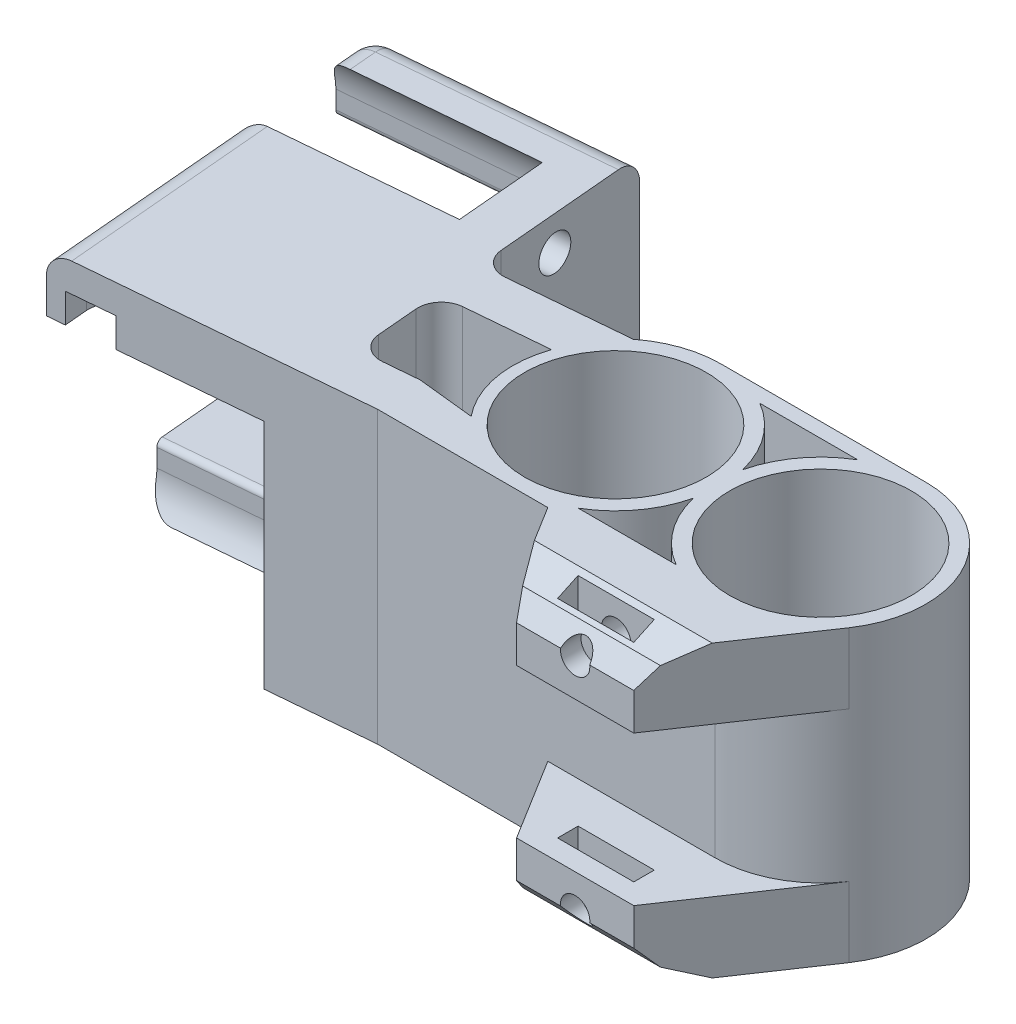
SolidWorks part; units mm, degrees
ref_plane "Front" through (0, 0, 0) normal (0, 0, 1) x (1, 0, 0)
ref_plane "Top" through (0, 0, 0) normal (0, 1, 0) x (1, 0, 0)
ref_plane "Right" through (0, 0, 0) normal (1, 0, 0) x (0, 0, -1)
sketch "Sketch1" plane through (0, 0, 0) normal (0, 1, 0) x (1, 0, 0)
  line L0 (0, 0) -> (17.5, 0) construction
  line L1 (0, 9) -> (17.5, 9)
  line L4 (0, -9) -> (17.5, -9)
  line L5 (0, -7.75) -> (17.5, -7.75)
  line L6 (0, 7.75) -> (17.5, 7.75)
  circle A6 centre (0, 0) radius 7.75
  circle A8 centre (0, 0) radius 7.75
  circle A10 centre (0, 0) radius 9
  circle A12 centre (17.5, 0) radius 7.75
  arc A13 (0, 9) -> (0, -9) centre (0, 0) ccw
  arc A14 (17.5, -9) -> (17.5, 9) centre (17.5, 0) ccw
  circle A15 centre (0, 0) radius 7.5 construction
  circle A16 centre (17.5, 0) radius 9
  point P5 (8.75, 0)
  dimension "D1" = 15.5
  dimension "D2" = 15.5
  dimension "D3" = 1.5
extrude "Boss-Extrude1" add sketch "Sketch1" along normal blind 24
sketch "Sketch2" plane through (0, 0, 0) normal (0, -1, 0) x (1, 0, 0)
  line L2 (17.5, 9) -> (0, 9)
  line L3 (0, -9) -> (17.5, -9)
  line L4 (17.5, 9) -> (0, 9)
  line L5 (0, -9) -> (17.5, -9)
  circle A0 centre (17.5, 0) radius 4.33 construction
  circle A1 centre (0, 0) radius 4.33 construction
  circle A2 centre (17.5, 0) radius 4.33
  circle A3 centre (0, 0) radius 4.33
  arc A6 (0, 9) -> (0, -9) centre (0, 0) ccw
  arc A7 (17.5, -9) -> (17.5, 9) centre (17.5, 0) ccw
  arc A8 (0, 9) -> (0, -9) centre (0, 0) ccw
  arc A9 (17.5, -9) -> (17.5, 9) centre (17.5, 0) ccw
  dimension "D1" = 0
extrude "Boss-Extrude2" add sketch "Sketch2" along normal blind 0.75
sketch "Sketch4" plane through (0, 0, 9) normal (0, 0, 1) x (1, 0, 0)
  line L0 (12.5625, -0.75) -> (12.5625, 24) construction
  line L1 (17.5, -0.75) -> (0, -0.75) construction
  line L3 (12.5625, 24) -> (12.5625, 11.625) construction
  line L4 (12.5625, 11.625) -> (0, 11.625) construction
  line L5 (0, 24) -> (0, -0.75) construction
  line L6 (17.5625, 5.25) -> (17.5625, -0.75)
  line L7 (17.5625, 5.25) -> (7.5625, 5.25)
  line L8 (17.5625, -0.75) -> (7.5625, -0.75)
  line L9 (7.5625, 5.25) -> (7.5625, -0.75)
  line L10 (17.5625, 5.25) -> (7.5625, -0.75) construction
  line L11 (17.5625, -0.75) -> (7.5625, 5.25) construction
  line L12 (17.5625, 18) -> (17.5625, 24)
  line L13 (17.5625, 24) -> (7.5625, 24)
  line L14 (7.5625, 18) -> (7.5625, 24)
  line L15 (17.5625, 18) -> (7.5625, 18)
  line L16 (16.1875, -135.4345) -> (16.1875, -151.4345) construction
  line L17 (8.9375, -151.4345) -> (8.9375, -135.4345) construction
  line L18 (16.1875, -135.4345) -> (16.1875, -151.4345) construction
  line L19 (8.9375, -151.4345) -> (8.9375, -135.4345) construction
  line L20 (8.9375, -143.4345) -> (16.1875, -143.4345) construction
  line L21 (16.1875, -143.4345) -> (12.5625, -143.4345) construction
  line L22 (12.5625, -143.4345) -> (12.5625, -5.1253) construction
  point P11 (12.5625, 2.25)
  dimension "D1" = 6
  dimension "D2" = 10
extrude "Boss-Extrude4" add sketch "Sketch4" along normal blind 7
sketch "Sketch5" plane through (0, 18, 0) normal (0, -1, 0) x (1, 0, 0)
  line L0 (9.3125, 12.5) -> (15.8125, 12.5)
  line L1 (9.3125, 12.5) -> (9.3125, 14.25)
  line L2 (15.8125, 12.5) -> (15.8125, 14.25)
  line L3 (9.3125, 14.25) -> (15.8125, 14.25)
  line L5 (12.5625, 16) -> (12.5625, 12.5) construction
  line L6 (7.5625, 16) -> (17.5625, 16) construction
  line L8 (7.5625, 9) -> (17.5, 9) construction
  dimension "D1" = 6.5
  dimension "D2" = 1.75
  dimension "D3" = 3.5
extrude "Cut-Extrude1" cut sketch "Sketch5" against normal through all both and the other way through all
sketch "Sketch6" plane through (0, 0, 16) normal (0, 0, 1) x (1, 0, 0)
  line L1 (7.5625, -0.75) -> (17.5625, -0.75) construction
  line L2 (17.5625, 24) -> (7.5625, 24) construction
  line L3 (12.5625, 24) -> (12.5625, 11.625) construction
  line L4 (12.5625, 11.625) -> (16.3282, 11.625) construction
  line L5 (12.5625, -0.75) -> (12.5625, 5.25) construction
  line L6 (17.5625, 5.25) -> (7.5625, 5.25) construction
  circle A0 centre (12.5625, 2.25) radius 1.25
  circle A1 centre (12.5625, 21) radius 1.25
  dimension "D1" = 2.5
extrude "Cut-Extrude2" cut sketch "Sketch6" against normal offset from surface (19 mm away) 6 up to face at (8.75, 11.625, -9)
sketch "Sketch7" plane through (0, 24, 0) normal (0, 1, 0) x (1, 0, 0)
  line L0 (-8.2702, -8.7348) -> (-9.6225, 6.7225) construction
  line L1 (8.75, 9) -> (8.75, 26.8601) construction
  line L2 (0, 9) -> (17.5, 9) construction
  line L3 (-8.2702, -8.7348) -> (-9.6225, 6.7225)
  line L4 (-8.2702, -8.7348) -> (-11.301, -9)
  line L5 (-9.6225, 6.7225) -> (16.4097, 9)
  line L6 (-6.5487, -14.069) -> (-8.9814, 13.7363)
  line L7 (-8.2702, -8.7348) -> (-9.6225, 6.7225)
  line L8 (-8.2702, -8.7348) -> (-20.2245, -9.7807)
  line L9 (-9.6225, 6.7225) -> (-21.5769, 5.6766)
  line L10 (-20.2245, -9.7807) -> (-21.5769, 5.6766)
  line L11 (0, 9) -> (17.5, 9) construction
  line L12 (0, 9) -> (17.5, 9)
  line L13 (7.5625, -9) -> (0, -9) construction
  line L14 (7.5625, -9) -> (0, -9)
  line L15 (0, -9) -> (-11.301, -9)
  line L22 (17.5625, -9) -> (17.5, -9)
  line L23 (17.5625, -9) -> (17.5, -9)
  line L24 (0, -9) -> (7.5625, -9)
  line L25 (7.5625, -9) -> (7.5625, -16)
  line L26 (0, -9) -> (7.5625, -9)
  line L27 (17.5, 9) -> (0, 9)
  line L28 (17.5625, -16) -> (17.5625, -9)
  line L29 (17.5625, -16) -> (17.5625, -9)
  line L30 (7.5625, -16) -> (17.5625, -16)
  line L31 (7.5625, -9) -> (7.5625, -16)
  line L32 (7.5625, -16) -> (17.5625, -16)
  line L33 (17.5, 9) -> (0, 9)
  arc A0 (0, 9) -> (0, -9) centre (0, 0) ccw construction
  circle A1 centre (0, 0) radius 7.75 construction
  arc A4 (17.5, -9) -> (17.5, 9) centre (17.5, 0) ccw
  arc A5 (0, 9) -> (0, -9) centre (0, 0) ccw
  arc A6 (17.5, -9) -> (17.5, 9) centre (17.5, 0) ccw
  arc A7 (0, 9) -> (0, -9) centre (0, 0) ccw
  line M21 (17.5, 9) -> (0, 9)
  arc M22 (0, 9) -> (0, -9) centre (0, 0) ccw
  dimension "D1" = 5
  dimension "D2" = 12
  dimension "D3" = 0
extrude "Boss-Extrude5" add sketch "Sketch7" against normal up to surface (24.75 mm away) contours L10 L8 L3 L9 | L6 L5 L3 M22 | L4 L6 L3 M22 | L6 M22 | L6 L5 M22 M21 | L15 L6 L4 M22
sketch "Sketch8" plane through (0, 24, 0) normal (0, 1, 0) x (1, 0, 0)
  line L1 (-11.6496, -5.0152) -> (-6.7762, -5.5359)
  line L2 (-11.301, -9) -> (-20.2245, -9.7807) construction
  line L3 (-11.301, -9) -> (-20.2245, -9.7807)
  line L4 (-20.2245, -9.7807) -> (-21.5769, 5.6766) construction
  line L5 (-20.2245, -9.7807) -> (-21.5769, 5.6766)
  line L8 (-11.6496, -5.0152) -> (-16.5884, -5.4473)
  line L9 (-16.5884, -5.4473) -> (-17.5921, 6.0252)
  line L11 (4.5758, 7.75) -> (12.9242, 7.75) construction
  line L12 (-5.2103, 3.0932) -> (-21.2282, 1.6918)
  line L13 (-8.2816, 2.8245) -> (-21.2282, 1.6918)
  line L14 (4.062, 7.75) -> (12.9242, 7.75)
  circle A2 centre (0, 0) radius 8.75
  circle A3 centre (0, 0) radius 8.75
  line M22 (4.5758, 7.75) -> (12.9242, 7.75)
  dimension "D1" = 4
  dimension "D2" = 4
  dimension "D3" = 1
extrude "Cut-Extrude3" cut sketch "Sketch8" against normal through all contours A3 L14 L13 L9 L8 L1 M22
sketch "Sketch9" plane through (-20.9201, 0, 1.8303) normal (-0.9962, 0, 0.0872) x (0.0872, 0, 0.9962)
  line L0 (-7.5356, 24) -> (-7.5356, -0.75)
  line L1 (-7.5356, 24) -> (-22.5356, 24)
  line L2 (-7.5356, -0.75) -> (-22.5356, -0.75)
  line L3 (-22.5356, 24) -> (-22.5356, -0.75)
  line L4 (-7.5356, -0.75) -> (7.9808, -0.75)
  line L5 (7.9808, -0.75) -> (7.9808, 24)
  line L6 (7.9808, 24) -> (-7.5356, 24)
  line L7 (-7.5356, 24) -> (-7.5356, -0.75)
  line L8 (-7.5356, -0.75) -> (7.9808, -0.75)
  line L9 (7.9808, -0.75) -> (7.9808, 24)
  line L10 (7.9808, 24) -> (-7.5356, 24)
  line L11 (-7.5356, 24) -> (-7.5356, -0.75)
  line M11 (-7.5356, 24) -> (-7.5356, -0.75)
  dimension "D2" = 15
  dimension "D1" = 0
extrude "Boss-Extrude6" add sketch "Sketch9" against normal up to surface (4 mm away) contours L1 L3 L2 M11 up to face at (-16.9159, 11.625, 1.7034)
fillet "Fillet1" radius 2 3 edges at (-17.5921, 11.625, -6.0252) (-17.2435, 11.625, -2.0405) (-16.5884, 11.625, 5.4473)
fillet "Fillet2" radius 2 2 edges at (-20.8918, -0.75, -20.7938) (-20.8918, 24, -20.7938)
sketch "Sketch13" plane through (-20.9201, 0, 1.8303) normal (-0.9962, 0, 0.0872) x (0.0872, 0, 0.9962)
  line L12 (-9.3456, 19.545) -> (-9.3456, 21.08)
  line L13 (-13.9706, 25.705) -> (-14.5706, 25.705)
  line L14 (-19.1956, 21.08) -> (-19.1956, 19.545)
  line L15 (7.9808, 19.045) -> (-22.5356, 19.045)
  line L16 (-18.6956, 21.08) -> (-18.6956, 19.545)
  line L17 (-19.6956, 18.545) -> (-8.8456, 18.545)
  line L18 (-9.8456, 19.545) -> (-9.8456, 21.08)
  line L19 (-13.9706, 25.205) -> (-14.5706, 25.205)
  line L20 (-18.6956, 21.08) -> (-18.6956, 19.545)
  line L21 (-19.6956, 18.545) -> (-8.8456, 18.545)
  line L22 (-9.8456, 19.545) -> (-9.8456, 21.08)
  line L23 (-13.9706, 25.205) -> (-14.5706, 25.205)
  line L36 (6.9544, 2.17) -> (6.9544, 3.9451)
  line L37 (7.3044, 4.705) -> (-2.8956, 4.705)
  line L38 (-1.8956, 3.705) -> (-1.8956, 2.17)
  line L39 (2.2294, -1.955) -> (2.8294, -1.955)
  line L40 (6.9544, 2.17) -> (6.9544, 3.9451)
  line L41 (7.3044, 4.705) -> (-2.8956, 4.705)
  line L42 (-1.8956, 3.705) -> (-1.8956, 2.17)
  line L43 (2.2294, -1.955) -> (2.8294, -1.955)
  line L48 (-2.3956, 3.705) -> (-2.3956, 2.17)
  line L49 (2.2294, -2.455) -> (2.8294, -2.455)
  line L50 (7.4544, 2.17) -> (7.4544, 3.9451)
  line L51 (-22.5356, 4.205) -> (5.8044, 4.205)
  line L53 (5.8044, 19.045) -> (-22.5356, 19.045) construction
  line L90 (-22.5356, 22) -> (-22.5356, 1.25)
  line L91 (-20.5356, -0.75) -> (7.9808, -0.75)
  line L92 (7.9808, -0.75) -> (7.9808, 24)
  line L93 (7.9808, 24) -> (-20.5356, 24)
  line L94 (-22.5356, 22) -> (-22.5356, 1.25)
  line L95 (-20.5356, -0.75) -> (7.9808, -0.75)
  line L96 (7.9808, -0.75) -> (7.9808, 24)
  line L97 (7.9808, 24) -> (-20.5356, 24)
  line L98 (-20.5356, 18.545) -> (-20.5356, 4.705)
  line L99 (-20.5356, 4.705) -> (5.8044, 4.705)
  line L100 (5.8044, 4.705) -> (5.8044, 18.545)
  line L101 (5.8044, 18.545) -> (-20.5356, 18.545)
  line L102 (-20.5356, 18.545) -> (-20.5356, 4.705)
  line L103 (-22.5356, 4.705) -> (5.8044, 4.705)
  line L104 (5.8044, 4.705) -> (5.8044, 18.545)
  line L105 (5.8044, 18.545) -> (-22.5356, 18.545)
  arc A8 (-9.3456, 19.545) -> (-8.8456, 19.045) centre (-8.8456, 19.545) ccw
  arc A9 (-9.3456, 21.08) -> (-13.9706, 25.705) centre (-13.9706, 21.08) ccw
  arc A10 (-14.5706, 25.705) -> (-19.1956, 21.08) centre (-14.5706, 21.08) ccw
  arc A11 (-19.6956, 19.045) -> (-19.1956, 19.545) centre (-19.6956, 19.545) ccw
  arc A12 (-2.3956, 3.705) -> (-2.8956, 4.205) centre (-2.8956, 3.705) ccw
  arc A13 (-2.3956, 2.17) -> (2.2294, -2.455) centre (2.2294, 2.17) ccw
  arc A14 (2.8294, -2.455) -> (7.4544, 2.17) centre (2.8294, 2.17) ccw
  arc A15 (7.6294, 4.325) -> (7.4544, 3.9451) centre (7.9544, 3.9451) ccw
  arc A36 (-22.5356, 1.25) -> (-20.5356, -0.75) centre (-20.5356, 1.25) ccw
  arc A37 (-20.5356, 24) -> (-22.5356, 22) centre (-20.5356, 22) ccw
  arc A38 (-19.6956, 18.545) -> (-18.6956, 19.545) centre (-19.6956, 19.545) ccw
  arc A39 (-9.8456, 19.545) -> (-8.8456, 18.545) centre (-8.8456, 19.545) ccw
  arc A40 (-9.8456, 21.08) -> (-13.9706, 25.205) centre (-13.9706, 21.08) ccw
  arc A41 (-14.5706, 25.205) -> (-18.6956, 21.08) centre (-14.5706, 21.08) ccw
  arc A42 (-19.6956, 18.545) -> (-18.6956, 19.545) centre (-19.6956, 19.545) ccw
  arc A43 (-9.8456, 19.545) -> (-8.8456, 18.545) centre (-8.8456, 19.545) ccw
  arc A70 (-9.8456, 21.08) -> (-13.9706, 25.205) centre (-13.9706, 21.08) ccw
  arc A72 (-14.5706, 25.205) -> (-18.6956, 21.08) centre (-14.5706, 21.08) ccw
  arc A74 (7.3044, 4.705) -> (6.9544, 3.9451) centre (7.9544, 3.9451) ccw
  arc A76 (-1.8956, 3.705) -> (-2.8956, 4.705) centre (-2.8956, 3.705) ccw
  arc A78 (-1.8956, 2.17) -> (2.2294, -1.955) centre (2.2294, 2.17) ccw
  arc A80 (2.8294, -1.955) -> (6.9544, 2.17) centre (2.8294, 2.17) ccw
  arc A82 (7.3044, 4.705) -> (6.9544, 3.9451) centre (7.9544, 3.9451) ccw
  arc A84 (-1.8956, 3.705) -> (-2.8956, 4.705) centre (-2.8956, 3.705) ccw
  arc A86 (-1.8956, 2.17) -> (2.2294, -1.955) centre (2.2294, 2.17) ccw
  arc A88 (2.8294, -1.955) -> (6.9544, 2.17) centre (2.8294, 2.17) ccw
  arc A90 (-22.5356, 1.25) -> (-20.5356, -0.75) centre (-20.5356, 1.25) ccw
  arc A92 (-20.5356, 24) -> (-22.5356, 22) centre (-20.5356, 22) ccw
  dimension "D1" = 0
  dimension "D2" = 0
  dimension "D3" = 0
  dimension "D4" = 0
  dimension "D5" = 0.5
  dimension "D6" = 0.5
extrude "Boss-Extrude9" add sketch "Sketch13" along normal up to surface (17.13 mm away)
sketch "Sketch14" plane through (-20.9201, 0, 1.8303) normal (-0.9962, 0, 0.0872) x (0.0872, 0, 0.9962)
  arc A0 (-14.5706, 22.955) -> (-14.5706, 19.205) centre (-14.5706, 21.08) ccw construction
  arc A1 (-14.5706, 22.955) -> (-14.5706, 19.205) centre (-14.5706, 21.08) ccw
  arc A2 (2.8294, 0.295) -> (2.8294, 4.045) centre (2.8294, 2.17) ccw construction
  arc A3 (2.8294, 0.295) -> (2.8294, 4.045) centre (2.8294, 2.17) ccw
  circle A4 centre (2.8294, 2.17) radius 1.5
  circle A5 centre (-14.5706, 21.08) radius 1.5
  dimension "D1" = 3
  dimension "D2" = 3
extrude "Cut-Extrude5" cut sketch "Sketch14" against normal blind 6 contours A5 | A4
sketch "Sketch15" plane through (0, 19.045, 0) normal (0, -1, 0) x (1, 0, 0)
  line L18 (-39.7015, -16.2974) -> (-39.949, -19.1266)
  line L19 (-39.949, -19.1266) -> (-22.8842, -20.6195)
  line L20 (-22.8842, -20.6195) -> (-22.6367, -17.7903)
  line L21 (-22.6367, -17.7903) -> (-39.7015, -16.2974)
  line L22 (-39.7015, -16.2974) -> (-39.949, -19.1266)
  line L23 (-39.949, -19.1266) -> (-22.8842, -20.6195)
  line L24 (-22.8842, -20.6195) -> (-22.6367, -17.7903)
  line L25 (-22.6367, -17.7903) -> (-39.7015, -16.2974)
  arc A1 (-24.8766, -20.4452) -> (-22.7099, -18.6271) centre (-24.7023, -18.4528) ccw construction
  arc A2 (-24.8766, -20.4452) -> (-22.7099, -18.6271) centre (-24.7023, -18.4528) ccw
  arc A3 (-24.894, -20.6445) -> (-22.5106, -18.6446) centre (-24.7023, -18.4528) ccw
  dimension "D2" = 0.2
  dimension "D3" = 0
extrude "Boss-Extrude10" add sketch "Sketch15" along normal up to surface (14.84 mm away) up to face at (-30.5607, 4.205, -10.0904)
fillet "Fillet4" radius 2 7 edges at (-38.0896, 24, 2.1263) (-38.9389, -0.75, -7.5815) (-39.898, -0.1642, -18.543) (-39.949, 2.7275, -19.1266) (-39.949, 20.5225, -19.1266) (-39.898, 23.4142, -18.543) (-39.6711, 24, -15.9495)
sketch "Sketch16" plane through (0.6956, 0, 7.9504) normal (0.0872, 0, 0.9962) x (0.9962, 0, -0.0872)
  line L0 (-36.63, 18.545) -> (-36.63, 4.705) construction
  line L1 (-36.63, 19.045) -> (-36.63, 4.705)
  line L3 (-36.63, 19.045) -> (-32.63, 19.045)
  line L4 (-36.63, 19.045) -> (-36.63, 21.545)
  line L5 (-36.63, 21.545) -> (-32.63, 21.545)
  line L6 (-32.63, 19.045) -> (-32.63, 21.545)
  line L8 (-12.0424, 24) -> (-36.13, 24)
  line L9 (-38.13, 22) -> (-38.13, 19.045)
  line L10 (-38.13, 19.045) -> (-21, 19.045)
  line L11 (-21, 19.045) -> (-21, -0.75)
  line L12 (-21, -0.75) -> (-12.0424, -0.75)
  line L13 (-12.0424, -0.75) -> (-12.0424, 24)
  line L14 (-12.0424, 24) -> (-36.13, 24)
  line L15 (-38.13, 22) -> (-38.13, 19.045)
  line L16 (-38.13, 19.045) -> (-21, 19.045)
  line L17 (-21, 19.045) -> (-21, -0.75)
  line L18 (-21, -0.75) -> (-12.0424, -0.75)
  line L19 (-12.0424, -0.75) -> (-12.0424, 24)
  arc A1 (-36.13, 24) -> (-38.13, 22) centre (-36.13, 22) ccw
  arc A2 (-36.13, 24) -> (-38.13, 22) centre (-36.13, 22) ccw
  line M13 (-38.13, 19.045) -> (-21, 19.045)
  dimension "D2" = 2.5
  dimension "D3" = 4
  dimension "D1" = 0
extrude "Cut-Extrude6" cut sketch "Sketch16" against normal blind 4 contours L6 L5 L4 M13
fillet "Fillet5" radius 2 2 edges at (-36.1437, 20.295, 7.1582) (-34.1513, 21.545, 6.9839)
sketch "Sketch17" plane through (0, -0.75, 0) normal (0, -1, 0) x (1, 0, 0)
  line L0 (17.5625, 16) -> (24.9609, 5.0334)
  line L4 (7.5625, 16) -> (-0.0278, 3.7366)
  line L18 (-21.0384, 0.4782) -> (-36.1108, 1.7969)
  line L19 (-36.1108, 1.7969) -> (-37.7823, -17.3085)
  line L20 (-37.7823, -17.3085) -> (-18.7251, -18.9758)
  line L21 (-18.7251, -18.9758) -> (-17.7664, -8.0176)
  line L22 (-15.5997, -6.1995) -> (-5.559, -7.078)
  line L23 (0, -9) -> (17.5, -9)
  line L24 (17.5, 9) -> (17.5625, 9)
  line L25 (17.5625, 9) -> (17.5625, 16)
  line L26 (17.5625, 16) -> (7.5625, 16)
  line L27 (7.5625, 16) -> (7.5625, 9)
  line L28 (7.5625, 9) -> (-11.301, 9)
  line L29 (-11.301, 9) -> (-20.2245, 9.7807)
  line L30 (-20.2245, 9.7807) -> (-21.0384, 0.4782)
  line L31 (-21.0384, 0.4782) -> (-36.1108, 1.7969)
  line L32 (-36.1108, 1.7969) -> (-37.7823, -17.3085)
  line L33 (-37.7823, -17.3085) -> (-18.7251, -18.9758)
  line L34 (-18.7251, -18.9758) -> (-17.7664, -8.0176)
  line L35 (-15.5997, -6.1995) -> (-5.559, -7.078)
  line L36 (0, -9) -> (17.5, -9)
  line L37 (17.5, 9) -> (17.5625, 9)
  line L38 (17.5625, 9) -> (17.5625, 16)
  line L39 (17.5625, 16) -> (7.5625, 16)
  line L40 (7.5625, 16) -> (7.5625, 9)
  line L41 (7.5625, 9) -> (-11.301, 9)
  line L42 (-11.301, 9) -> (-20.2245, 9.7807)
  line L43 (-20.2245, 9.7807) -> (-21.0384, 0.4782)
  arc A0 (17.5, -9) -> (17.5, 9) centre (17.5, 0) ccw construction
  arc A4 (-15.5997, -6.1995) -> (-17.7664, -8.0176) centre (-15.774, -8.1919) ccw
  arc A5 (-5.559, -7.078) -> (0, -9) centre (0, 0) ccw
  arc A6 (17.5, -9) -> (17.5, 9) centre (17.5, 0) ccw
  arc A7 (-15.5997, -6.1995) -> (-17.7664, -8.0176) centre (-15.774, -8.1919) ccw
  arc A8 (-5.559, -7.078) -> (0, -9) centre (0, 0) ccw
  arc A9 (17.5, -9) -> (17.5, 9) centre (17.5, 0) ccw
  arc M27 (17.5, -9) -> (17.5, 9) centre (17.5, 0) ccw
  line M28 (17.5, 9) -> (17.5625, 9)
  line M29 (17.5625, 9) -> (17.5625, 16)
  line M31 (7.5625, 16) -> (7.5625, 9)
  line M32 (7.5625, 9) -> (-11.301, 9)
  dimension "D1" = 0
extrude "Boss-Extrude11" add sketch "Sketch17" against normal up to surface (6 mm away) contours L4 M31 M32 | L0 M29 M28 M27 up to face at (12.5625, 5.25, 13.375)
sketch "Sketch18" plane through (0, 24, 0) normal (0, 1, 0) x (1, 0, 0)
  line L4 (3.23, -9) -> (7.5625, -16)
  line L6 (3.23, -9) -> (7.5625, -16)
  line L10 (17.5, -9) -> (3.23, -9)
  line L12 (7.5625, -16) -> (17.5625, -16)
  line L13 (17.5625, -16) -> (24.9609, -5.0334)
  line L18 (17.5, -9) -> (3.23, -9)
  line L20 (7.5625, -16) -> (17.5625, -16)
  line L21 (17.5625, -16) -> (24.9609, -5.0334)
  line L31 (-18.7251, 18.9758) -> (-37.7823, 17.3085)
  line L32 (-37.7823, 17.3085) -> (-37.575, 14.9392)
  line L33 (-37.575, 14.9392) -> (-22.5026, 16.2579)
  line L34 (-22.5026, 16.2579) -> (-21.8251, 8.5141)
  line L35 (-21.8251, 8.5141) -> (-36.8975, 7.1954)
  line L36 (-36.8975, 7.1954) -> (-35.2969, -11.0994)
  line L37 (-35.2969, -11.0994) -> (-11.301, -9)
  line L38 (-11.301, -9) -> (7.5625, -9)
  line L39 (7.5625, -9) -> (7.5625, -16)
  line L40 (7.5625, -16) -> (17.5625, -16)
  line L41 (17.5625, -16) -> (17.5625, -9)
  line L42 (17.5625, -9) -> (17.5, -9)
  line L43 (17.5, 9) -> (0, 9)
  line L44 (-5.559, 7.078) -> (-15.5997, 6.1995)
  line L45 (-17.7664, 8.0176) -> (-18.7251, 18.9758)
  line L46 (-18.7251, 18.9758) -> (-37.7823, 17.3085)
  line L47 (-37.7823, 17.3085) -> (-37.575, 14.9392)
  line L48 (-37.575, 14.9392) -> (-22.5026, 16.2579)
  line L49 (-22.5026, 16.2579) -> (-21.8251, 8.5141)
  line L50 (-21.8251, 8.5141) -> (-36.8975, 7.1954)
  line L51 (-36.8975, 7.1954) -> (-35.2969, -11.0994)
  line L52 (-35.2969, -11.0994) -> (-11.301, -9)
  line L53 (-11.301, -9) -> (7.5625, -9)
  line L54 (7.5625, -9) -> (7.5625, -16)
  line L55 (7.5625, -16) -> (17.5625, -16)
  line L56 (17.5625, -16) -> (17.5625, -9)
  line L57 (17.5625, -9) -> (17.5, -9)
  line L58 (17.5, 9) -> (0, 9)
  line L59 (-5.559, 7.078) -> (-15.5997, 6.1995)
  line L60 (-17.7664, 8.0176) -> (-18.7251, 18.9758)
  arc A1 (17.5, -9) -> (24.9609, -5.0334) centre (17.5, 0) ccw
  arc A2 (17.5, -9) -> (24.9609, -5.0334) centre (17.5, 0) ccw
  arc A5 (17.5, -9) -> (17.5, 9) centre (17.5, 0) ccw
  arc A6 (0, 9) -> (-5.559, 7.078) centre (0, 0) ccw
  arc A7 (-17.7664, 8.0176) -> (-15.5997, 6.1995) centre (-15.774, 8.1919) ccw
  arc A8 (17.5, -9) -> (17.5, 9) centre (17.5, 0) ccw
  arc A9 (0, 9) -> (-5.559, 7.078) centre (0, 0) ccw
  arc A10 (-17.7664, 8.0176) -> (-15.5997, 6.1995) centre (-15.774, 8.1919) ccw
  line M36 (-11.301, -9) -> (7.5625, -9)
  line M37 (7.5625, -9) -> (7.5625, -16)
  line M39 (17.5625, -16) -> (17.5625, -9)
  line M40 (17.5625, -9) -> (17.5, -9)
  arc M41 (17.5, -9) -> (17.5, 9) centre (17.5, 0) ccw
  dimension "D1" = 0
  dimension "D2" = 0
extrude "Boss-Extrude12" add sketch "Sketch18" against normal up to surface (6 mm away) contours L21 M39 M41 M40 | L6 M36 M37 up to face at (12.5625, 18, 13.375)
chamfer "Chamfer1" distance 4 angle 25 2 edges at (12.5625, 24, 16) (12.5625, -0.75, 16)
chamfer "Chamfer2" distance 1.5 angle 25 2 edges at (15.3246, 22.1348, 16) (15.3246, 1.1152, 16)
